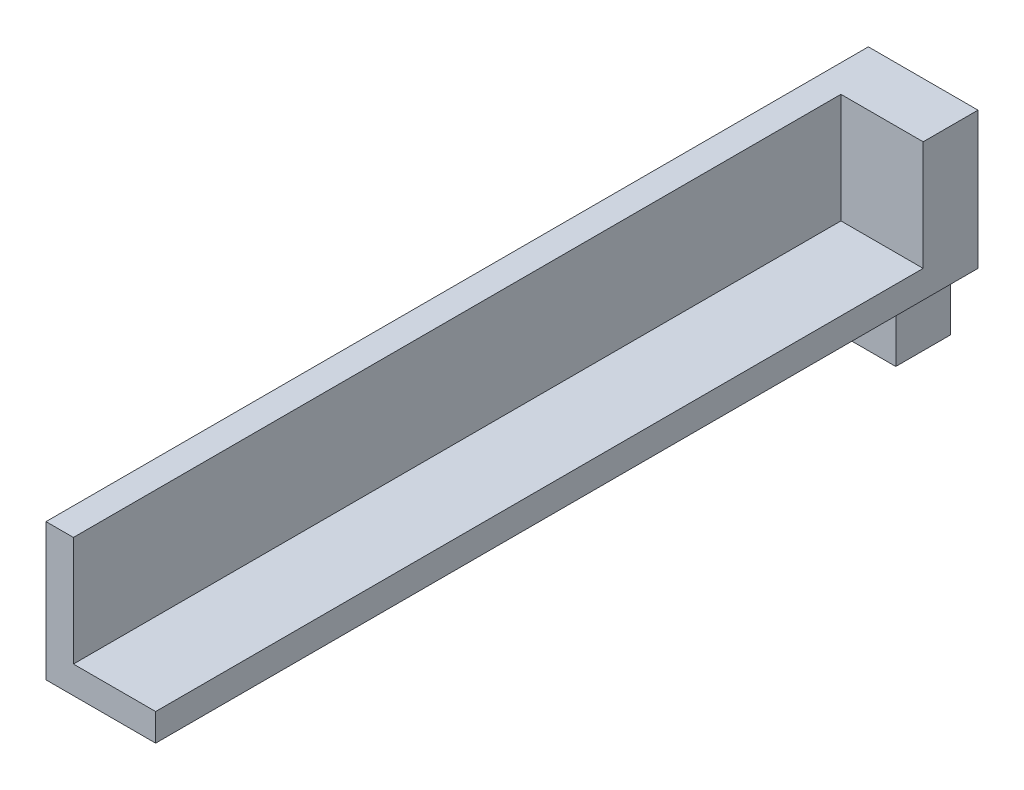
SolidWorks part; units mm, degrees
ref_plane "Front Plane" through (0, 0, 0) normal (0, 0, 1) x (1, 0, 0)
ref_plane "Top Plane" through (0, 0, 0) normal (0, 1, 0) x (1, 0, 0)
ref_plane "Right Plane" through (0, 0, 0) normal (1, 0, 0) x (0, 0, -1)
sketch "Sketch1" plane through (0, 0, 0) normal (1, 0, 0) x (0, 0, -1)
  line L0 (0, -1509.5556) -> (0, 73968.222) construction
  line L1 (0, 0) -> (-10, 0)
  line L2 (-10, 0) -> (-10, -20)
  line L3 (-10, -20) -> (-30, -20)
  line L6 (0, -38) -> (0, 0)
  line L7 (-30, -20) -> (-30, -25)
  line L8 (-30, -25) -> (-10, -25)
  line L9 (-10, -25) -> (-10, -38)
  line L10 (-10, -38) -> (0, -38)
  dimension "D1" = 20
  dimension "D2" = 20
  dimension "D3" = 5
  dimension "D4" = 10
  dimension "D5" = 10
  dimension "D6" = 38
extrude "Boss-Extrude1" add sketch "Sketch1" along normal blind 10
sketch "Sketch2" plane through (0, 0, 0) normal (-1, 0, 0) x (0, 0, 1)
  line L1 (0, 0) -> (30, 0)
  line L2 (0, 0) -> (0, -25)
  line L3 (0, -25) -> (30, -25)
  line L4 (30, 0) -> (30, -25)
extrude "Boss-Extrude2" add sketch "Sketch2" along normal blind 5
sketch "Sketch3" plane through (10, 0, 0) normal (1, 0, 0) x (0, 0, -1)
  line L0 (-10, 0) -> (-10, -20)
  line L1 (-10, -20) -> (-30, -20)
  line L2 (-30, -20) -> (-30, -25)
  line L3 (-30, -25) -> (-10, -25)
  line L4 (-10, -25) -> (0, -25)
  line L5 (0, -25) -> (0, 0)
  line L6 (0, 0) -> (-10, 0)
extrude "Boss-Extrude3" add sketch "Sketch3" along normal blind 5
sketch "Sketch4" plane through (0, 0, 30) normal (0, 0, 1) x (1, 0, 0)
  line L0 (-5, 0) -> (-5, -25)
  line L1 (-5, -25) -> (15, -25)
  line L2 (15, -25) -> (15, -20)
  line L3 (15, -20) -> (0, -20)
  line L4 (0, -20) -> (0, 0)
  line L5 (0, 0) -> (-5, 0)
extrude "Boss-Extrude4" add sketch "Sketch4" along normal up to surface (120 mm away) up to face at (3.3333, -15, 30)
